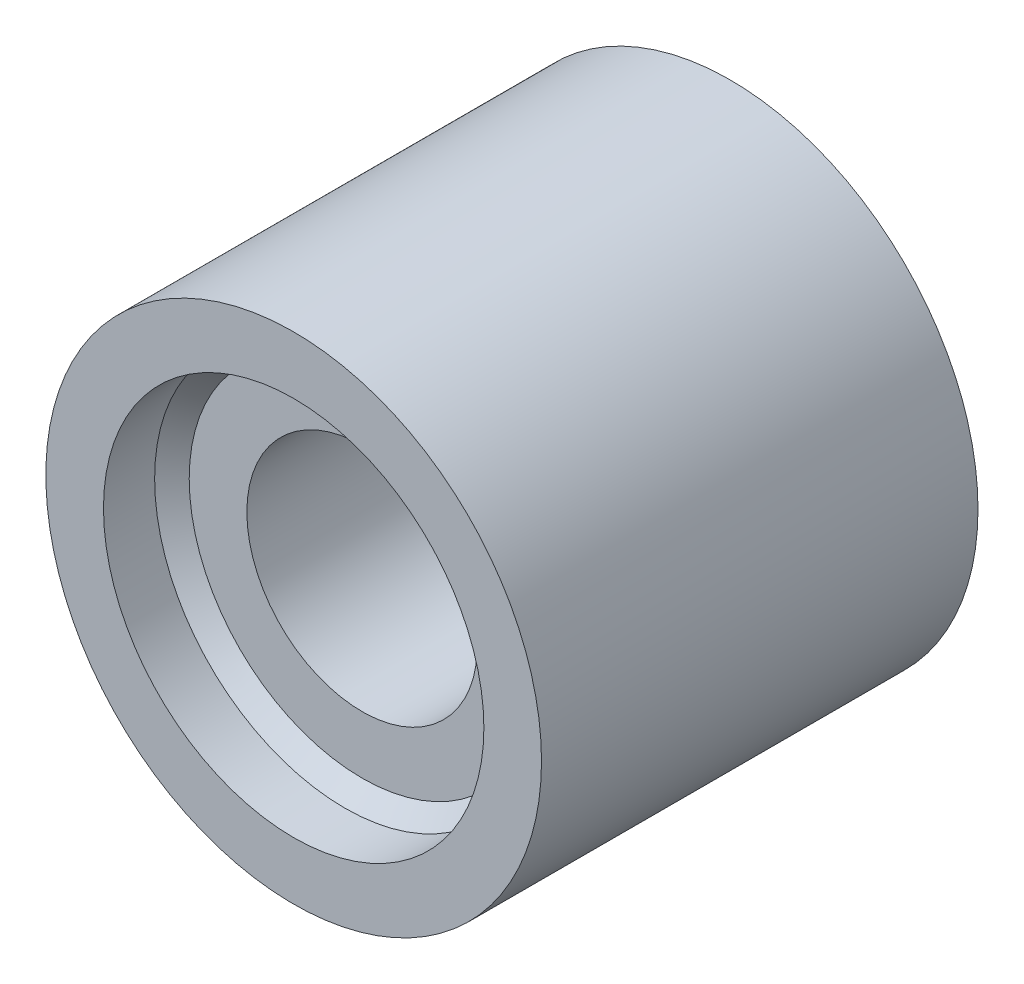
SolidWorks part; units mm, degrees
material "6061 Alloy"
ref_plane "Front Plane" through (0, 0, 0) normal (0, 0, 1) x (1, 0, 0)
ref_plane "Top Plane" through (0, 0, 0) normal (0, 1, 0) x (1, 0, 0)
ref_plane "Right Plane" through (0, 0, 0) normal (1, 0, 0) x (0, 0, -1)
sketch "Sketch1" plane through (0, 0, 0) normal (0, 0, 1) x (1, 0, 0)
  circle A0 centre (0, 0) radius 5.08
  circle A1 centre (0, 0) radius 8.382
  circle A2 centre (0, 0) radius 10.922
  dimension "D1" = 10.16
  dimension "D2" = 16.764
  dimension "D3" = 2.54
extrude "Boss-Extrude1" add sketch "Sketch1" along normal mid plane 19.2354 contours A2 A1 region at (-10.6131, 0, 0)
extrude "Boss-Extrude2" add sketch "Sketch1<3>" along normal mid plane 13.2029 contours A1 A0 region at (-8.1449, 0, 0)
sketch "Sketch1<3>" plane through (0, 0, 0) normal (0, 0, 1) x (1, 0, 0) same geometry as "Sketch1"
chamfer "Chamfer1" distance 0.762 angle 45 2 edges at (8.382, 0, -6.6015) (8.382, 0, 6.6015)
equation "\"gap\"= 0.8198"
equation "\"ID\"= 0.40"
equation "\"Bearing Dia\"= .640"
equation "\"thick\"= .1"
equation "\"D1@Sketch1\"=\"ID\""
equation "\"D2@Sketch1\"=\"Bearing Dia\"+.02"
equation "\"D3@Sketch1\"=\"thick\""
equation "\"D1@Boss-Extrude2\"=\"gap\"-.3"
equation "\"D1@Boss-Extrude1\"=\"gap\"-2/32"
